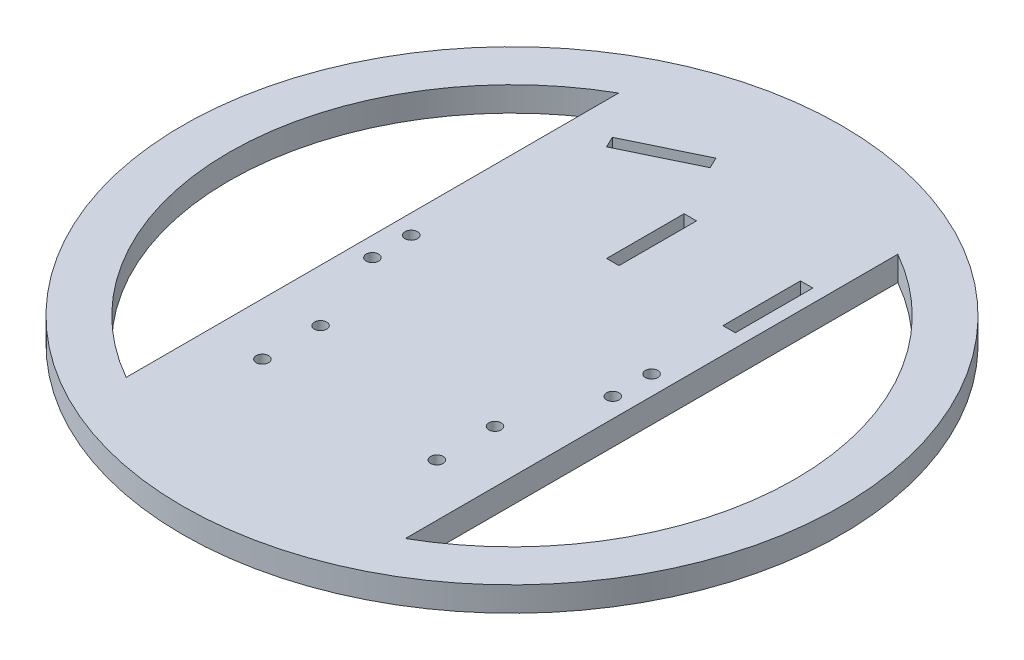
SolidWorks part; units mm, degrees
material "Acrylic (Medium-high impact)"
ref_plane "Front Plane" through (0, 0, 0) normal (0, 0, 1) x (1, 0, 0)
ref_plane "Top Plane" through (0, 0, 0) normal (0, 1, 0) x (1, 0, 0)
ref_plane "Right Plane" through (0, 0, 0) normal (1, 0, 0) x (0, 0, -1)
sketch "Sketch1" plane through (0, 0, 0) normal (0, 1, 0) x (1, 0, 0)
  line L0 (0, 0) -> (0, 85) construction
  line L1 (16, 0) -> (16, 83.4805) construction
  line L2 (-36, 63.5059) -> (-36, -63.5059)
  line L3 (-8.9296, 61.5082) -> (-26.9335, 52.7986)
  line L4 (36, 63.5059) -> (36, -63.5059)
  line L5 (-36, 63.5059) -> (36, -63.5059) construction
  line L6 (-36, -63.5059) -> (36, 63.5059) construction
  line L7 (-0.6, 45) -> (-0.6, 25)
  line L8 (-0.6, 25) -> (2.6, 25)
  line L9 (2.6, 45) -> (2.6, 25)
  line L10 (-0.6, 45) -> (2.6, 25) construction
  line L11 (-0.6, 25) -> (2.6, 45) construction
  line L12 (32.6, 25) -> (29.4, 45) construction
  line L13 (32.6, 45) -> (29.4, 25) construction
  line L14 (29.4, 45) -> (29.4, 25)
  line L15 (32.6, 25) -> (29.4, 25)
  line L16 (32.6, 45) -> (32.6, 25)
  line L17 (32.6, 45) -> (29.4, 45)
  line L18 (-8.9296, 61.5082) -> (-7.5361, 58.6276)
  line L19 (-7.5361, 58.6276) -> (-25.54, 49.9179)
  line L20 (-25.54, 49.9179) -> (-26.9335, 52.7986)
  line L21 (-0.6, 45) -> (2.6, 45)
  circle A0 centre (0, 0) radius 85
  arc A1 (36, -63.5059) -> (36, 63.5059) centre (0, 0) ccw
  arc A2 (-36, 63.5059) -> (-36, -63.5059) centre (0, 0) ccw
  point P3 (1, 35)
  point P19 (31, 35)
  dimension "D1" = 170
  dimension "D2" = 12
  dimension "D3" = 72
  dimension "D4" = 30
  dimension "D5" = 3.2
  dimension "D6" = 20
  dimension "D7" = 5
  dimension "D8" = 35
  dimension "D9" = 3.2
  dimension "D10" = 20
extrude "Boss-Extrude1" add sketch "Sketch1" along normal blind 6.35
hole_wizard "CBORE for M3 SHCS1" positions "Sketch2" profile "Sketch3" counterbore size "M3" standard "ANSI Metric" end condition through all
sketch "Sketch2" plane through (0, 0, 0) normal (0, -1, 0) x (-1, 0, 0)
  line L0 (0, 0) -> (-36, 0) construction
  line L1 (-36, 63.5059) -> (-36, -63.5059) construction
  line L3 (0, 0) -> (0, 85) construction
  circle A0 centre (0, 0) radius 85 construction
  point P0 (-31, 5)
  point P19 (-31, -5)
  point P21 (31, 5)
  point P22 (31, -5)
  dimension "D1" = 10
  dimension "D2" = 5
sketch "Sketch3" plane through (31, 0, -5) normal (1, 0, 0) x (0, 0, -1)
  line L0 (0, 0) -> (0, 6.35)
  line L1 (0, 6.35) -> (1.6, 6.35)
  line L3 (1.6, 6.35) -> (1.6, 3.5)
  line L4 (1.6, 3.5) -> (3.75, 3.5)
  line L5 (3.75, 3.5) -> (3.75, 0)
  line L7 (3.75, 0) -> (0, 0)
  line L11 (0, -6.35) -> (0, 107.95) construction
  dimension "Thru Hole Dia." = 3.2
  dimension "Thru Hole Depth" = 6.35
  dimension "C'Bore Dia." = 7.5
  dimension "C'Bore Depth" = 3.5
hole_wizard "CBORE for M3 SHCS2" positions "Sketch5" profile "Sketch6" counterbore size "M3" standard "ANSI Metric" end condition through all
sketch "Sketch5" plane through (0, 0, 0) normal (0, -1, 0) x (-1, 0, 0)
  line L0 (0, 0) -> (0, -85) construction
  line L3 (0, -43.6871) -> (-33, -43.6871) construction
  circle A0 centre (0, 0) radius 85 construction
  point P0 (22.5, -26.8871)
  point P12 (-22.5, -26.8871)
  point P33 (22.5, -41.8871)
  point P34 (-22.5, -41.8871)
  dimension "D1" = 45
  dimension "D2" = 16.8
  dimension "D3" = 54.75
  dimension "D4" = 10.5
  dimension "D5" = 2
sketch "Sketch6" plane through (-22.5, 0, 26.8871) normal (1, 0, 0) x (0, 0, -1)
  line L0 (0, 0) -> (0, 6.35)
  line L1 (0, 6.35) -> (1.6, 6.35)
  line L3 (1.6, 6.35) -> (1.6, 3.5)
  line L4 (1.6, 3.5) -> (3.75, 3.5)
  line L5 (3.75, 3.5) -> (3.75, 0)
  line L7 (3.75, 0) -> (0, 0)
  line L11 (0, -6.35) -> (0, 107.95) construction
  dimension "Thru Hole Dia." = 3.2
  dimension "Thru Hole Depth" = 6.35
  dimension "C'Bore Dia." = 7.5
  dimension "C'Bore Depth" = 3.5
sketch "Sketch7" plane through (0, 0, 0) normal (0, -1, 0) x (1, 0, 0)
  line L0 (0, 0) -> (0, -26.4572) construction
  line L1 (10.2, -1) -> (2.2, -1)
  line L3 (-10.2, -39) -> (-2.2, -39)
  line L7 (-10.2, -39) -> (-10.2, -1)
  line L8 (-10.2, -1) -> (-2.2, -1)
  line L9 (-2.2, -39) -> (-2.2, -1)
  line L10 (-10.2, -39) -> (-2.2, -1) construction
  line L11 (-10.2, -1) -> (-2.2, -39) construction
  line L12 (10.2, -39) -> (2.2, -1) construction
  line L13 (10.2, -1) -> (2.2, -39) construction
  line L14 (2.2, -39) -> (2.2, -1)
  line L15 (10.2, -39) -> (2.2, -39)
  line L16 (10.2, -39) -> (10.2, -1)
  line L17 (29, -36) -> (21, -64) construction
  line L18 (-29, -64) -> (-21, -64)
  line L19 (-29, -64) -> (-29, -36)
  line L20 (-29, -36) -> (-21, -36)
  line L21 (-21, -64) -> (-21, -36)
  line L22 (-29, -64) -> (-21, -36) construction
  line L23 (-29, -36) -> (-21, -64) construction
  line L24 (29, -64) -> (21, -36) construction
  line L25 (29, -36) -> (21, -36)
  line L26 (21, -64) -> (21, -36)
  line L27 (29, -64) -> (21, -64)
  line L28 (29, -64) -> (29, -36)
  point P3 (-6.2, -20)
  point P17 (6.2, -20)
  point P18 (-25, -50)
  point P23 (25, -50)
  dimension "D2" = 20
  dimension "D4" = 8
  dimension "D5" = 38
  dimension "D7" = 12.4
  dimension "D8" = 28
  dimension "D9" = 8
  dimension "D10" = 50
  dimension "D11" = 50
extrude "Cut-Extrude1" cut sketch "Sketch7" against normal blind 3.5
